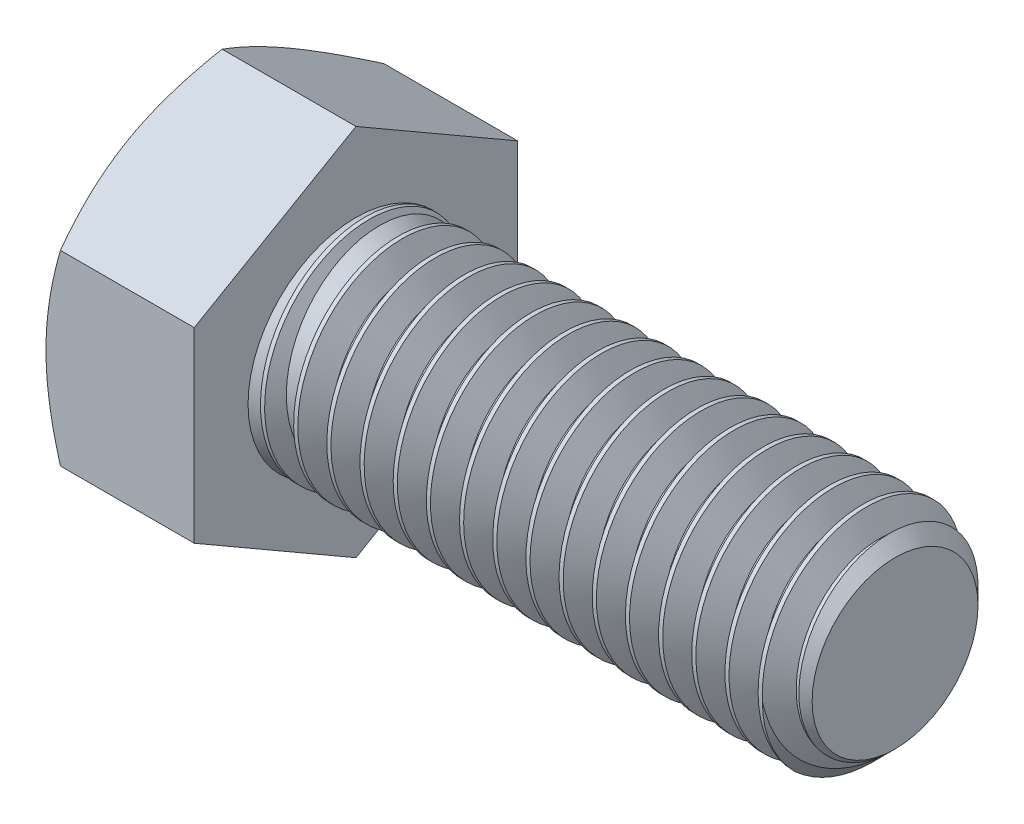
SolidWorks part; units mm, degrees
note: '?' marks a value the reader was unsure of.
ref_plane "Front Plane" through (0, 0, 0) normal (0, 0, 1) x (1, 0, 0)
ref_plane "Top Plane" through (0, 0, 0) normal (0, 1, 0) x (1, 0, 0)
ref_plane "Right Plane" through (0, 0, 0) normal (1, 0, 0) x (0, 0, -1)
sketch "Sketch1" plane through (0, 0, 0) normal (0, 0, 1) x (1, 0, 0)
  line L0 (-20.2406, 0) -> (20.2406, 0) construction
  line L1 (20.2406, 6.35) -> (20.2406, -6.35) construction
  line L2 (-11.5094, 9.525) -> (-11.5094, -9.525) construction
  line L3 (-20.2406, 9.525) -> (-20.2406, -9.525) construction
  line L4 (-11.7634, 6.3562) -> (-11.5094, 6.3562) construction
  line L5 (-11.5094, 6.3562) -> (-0.5001, 0) construction
  line L6 (-11.7634, 6.3562) -> (-11.7634, 0) construction
  line L7 (-11.5094, 0) -> (-11.5094, 6.3562) construction
  point P9 (-11.5094, 0)
  point P10 (13.4022, -6.35)
  dimension "Screw Dia" = 12.7
  dimension "Hex" = 19.05
  dimension "Head Ht" = 8.7312
  dimension "Screw Length" = 31.75
  dimension "D1" = 6.8385
  dimension "D2" = 30
  dimension "D3" = 0.254
  dimension "MinThread" = 31.75
  dimension "D4" = 0.0124
ref_plane "Plane2" through (20.2406, 0, 0) normal (1, 0, 0) x (0, 0, -1)
sketch "Sketch5" plane through (20.2406, 0, 0) normal (1, 0, 0) x (0, 0, -1)
  circle A0 centre (0, 0) radius 6.35
extrude "Boss-Extrude3" add sketch "Sketch5" against normal up to vertex (31.75 mm away) up to point (-11.5094, 0, 0)
sketch "Sketch9" plane through (20.2406, 0, 0) normal (1, 0, 0) x (0, 0, -1)
  circle A1 centre (0, 0) radius 6.35
  circle A2 centre (0, 0) radius 6.35
  dimension "D1" = 0
chamfer "Chamfer1" distance 1.4654 angle 45 1 edges at (20.2406, 0, -6.35)
sketch "Sketch6" plane through (-11.5094, 0, 0) normal (-1, 0, 0) x (0, 0, 1)
  line L0 (0, 9.525) -> (0, -9.525) construction
  line L1 (9.525, 5.4993) -> (0, 10.9985)
  line L2 (0, 10.9985) -> (-9.525, 5.4993)
  line L3 (-9.525, 5.4993) -> (-9.525, -5.4993)
  line L4 (-9.525, -5.4993) -> (0, -10.9985)
  line L5 (0, -10.9985) -> (9.525, -5.4993)
  line L6 (9.525, -5.4993) -> (9.525, 5.4993)
  circle A0 centre (0, 0) radius 9.525 construction
extrude "Boss-Extrude4" add sketch "Sketch6" along normal up to vertex (8.7312 mm away) separate body up to point (-20.2406, -9.525, 0)
sketch "Sketch7" plane through (-20.2406, 0, 0) normal (-1, 0, 0) x (0, 0, 1)
  circle A0 centre (0, 0) radius 9.525 construction
  circle A1 centre (0, 0) radius 9.525
sketch "Sketch8" plane through (-20.2406, 0, 0) normal (-1, 0, 0) x (0, 0, 1)
  circle A0 centre (0, 0) radius 9.525 construction
  circle A1 centre (0, 0) radius 9.525
extrude "Cut-Extrude3" cut sketch "Sketch8" against normal through all draft 60 flip side to cut
sketch "Sketch12" plane through (-20.2406, 0, 0) normal (-1, 0, 0) x (0, 0, 1)
  line L0 (0, 7.3342) -> (0, 4.0958) construction
  line L1 (0.2857, 7.3342) -> (0.2858, 4.0958)
  line L2 (-0.2858, 7.3342) -> (-0.2857, 4.0958)
  line L3 (0, 6.35) -> (0, -6.35) construction
  arc A0 (0.2857, 7.3342) -> (-0.2858, 7.3342) centre (0, 7.3342) ccw
  arc A1 (-0.2857, 4.0958) -> (0.2858, 4.0958) centre (0, 4.0958) ccw
  circle A3 centre (0, 0) radius 3.81 construction
  circle A4 centre (0, 0) radius 7.62 construction
  point P2 (0, 5.715)
  dimension "D1" = 7.62
  dimension "D3" = 15.24
  dimension "D2" = 0.5715
extrude "Cut-Extrude4" cut sketch "Sketch12" against normal blind 0.254
pattern_circular "CirPattern1" count 6 over 360 about axis through (0, 0, 0) along (1, 0, 0) of "Cut-Extrude4"
curve "Helix/Spiral1" pitch 1.9538 height 33.7038 turns 17.25 parameters "Pitch"=1.9538
sketch "Sketch10" plane through (0, 0, 0) normal (0, 0, 1) x (1, 0, 0)
  line L0 (20.2406, 6.35) -> (20.9733, 5.0809)
  line L1 (20.9733, 5.0809) -> (21.2175, 5.0809)
  line L2 (21.2175, 5.0809) -> (21.9502, 6.35)
  line L3 (20.2406, 6.35) -> (21.9502, 6.35)
  line L4 (21.0954, 6.35) -> (21.0954, 5.0809) construction
  line L5 (20.607, 5.7155) -> (21.5839, 5.7155) construction
  dimension "D1" = 60
  dimension "D2" = 0.2442
  dimension "D3" = 0.9769
sweep "Cut-Sweep1" cut profiles "Sketch10" path "Helix/Spiral1" align with end faces yes
sketch "Sketch13" plane through (0, 0, 0) normal (0, 0, 1) x (1, 0, 0)
  line L0 (-20.2406, 0) -> (20.2406, 0) construction
  line L1 (-11.5094, 6.3562) -> (-0.5001, 0) construction
  line L2 (-11.7634, 6.3562) -> (-11.5094, 6.3562) construction
  line L3 (-11.7634, 6.3562) -> (-11.7634, 0) construction
  line L4 (-11.7634, 0) -> (-0.5001, 0)
  line L5 (-11.5094, 6.3562) -> (-0.5001, 0)
  line L6 (-11.7634, 6.3562) -> (-11.5094, 6.3562)
  line L7 (-11.7634, 6.3562) -> (-11.7634, 0)
revolve "Revolve7" add sketch "Sketch13" angle 360 about L4
ref_axis "Center Axis 1" through (-11.4986, 0, 0) along (1, 0, 0)?
ref_plane "Contact Plane 1" through (-11.5094, 0, 0) normal (1, 0, 0) x (0, 0, -1)
equation "\"D2@Sketch10\" = \"Pitch@Helix/Spiral1\"*.125"
equation "\"D3@Sketch10\" = \"Pitch@Helix/Spiral1\"*.5"
equation "\"D3@Helix/Spiral1\" = \"Screw Length@Sketch1\" + \"Pitch@Helix/Spiral1\""
equation "\"D1@Chamfer1\" = \"Pitch@Helix/Spiral1\"*.75"
equation "\"D1@Sketch12\" = \"Hex@Sketch1\"*.4"
equation "\"D3@Sketch12\" = \"Hex@Sketch1\"*.8"
equation "\"D2@Sketch12\" = \"Hex@Sketch1\"*.03"
equation "\"D1@Sketch1\" = \"Pitch@Helix/Spiral1\"*3.5"
